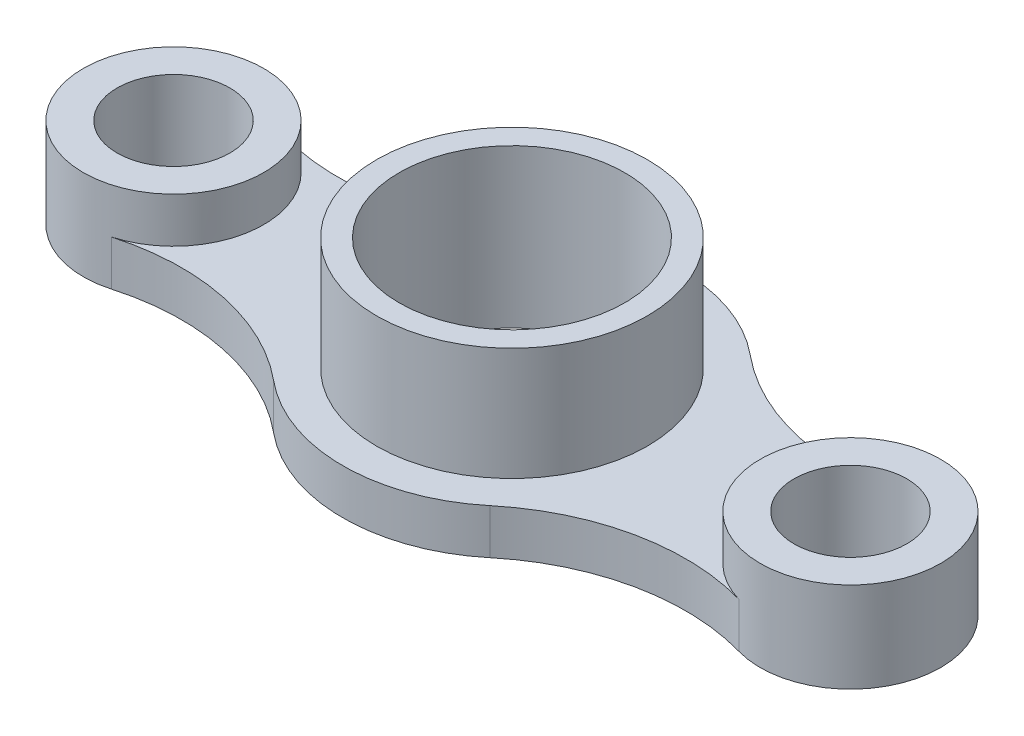
SolidWorks part; units mm, degrees
ref_plane "Front Plane" through (0, 0, 0) normal (0, 0, 1) x (1, 0, 0)
ref_plane "Top Plane" through (0, 0, 0) normal (0, 1, 0) x (1, 0, 0)
ref_plane "Right Plane" through (0, 0, 0) normal (1, 0, 0) x (0, 0, -1)
sketch "Sketch1" plane through (0, 0, 0) normal (0, 1, 0) x (1, 0, 0)
  line L0 (0, -5.5) -> (0, 5.5) construction
  circle A0 centre (0, 0) radius 50
  arc A1 (-139.0714, 38.4781) -> (-139.0714, -38.4781) centre (-150, 0) ccw
  circle A3 centre (0, 0) radius 60
  arc A4 (47.8929, 57.7172) -> (-47.8929, 57.7172) centre (0, 0) ccw
  circle A5 centre (-150, 0) radius 25
  arc A6 (-139.0714, 38.4781) -> (-47.8929, 57.7172) centre (-111.75, 134.6734) ccw
  arc A7 (-139.0714, -38.4781) -> (-47.8929, -57.7172) centre (-111.75, -134.6734) cw
  arc A8 (139.0714, -38.4781) -> (47.8929, -57.7172) centre (111.75, -134.6734) ccw
  arc A9 (139.0714, 38.4781) -> (47.8929, 57.7172) centre (111.75, 134.6734) cw
  circle A10 centre (150, 0) radius 25
  arc A11 (139.0714, 38.4781) -> (139.0714, -38.4781) centre (150, 0) cw
  arc A12 (-47.8929, -57.7172) -> (47.8929, -57.7172) centre (0, 0) ccw
  point P14 (-91.1042, 36.8279)
  dimension "D2" = 100
  dimension "D3" = 120
  dimension "D4" = 150
  dimension "D5" = 80
  dimension "D6" = 50
  dimension "D7" = 100
  dimension "D8" = 100
  dimension "D1" = 150
extrude "Boss-Extrude2" add sketch "Sketch1" along normal blind 20 contours A1 A7 A12 A8 A11 A9 A4 A6 | A3 | A10 | A5
extrude "Boss-Extrude3" add sketch "Sketch1<7>" along normal blind 70 contours A3 | A0
sketch "Sketch1<7>" plane through (0, 0, 0) normal (0, 1, 0) x (1, 0, 0) same geometry as "Sketch1"
sketch "Sketch3" plane through (0, 20, 0) normal (0, 1, 0) x (1, 0, 0)
  circle A0 centre (-150, 0) radius 40
  circle A1 centre (-150, 0) radius 25
  dimension "D1" = 80
  dimension "D2" = 50
extrude "Boss-Extrude4" add sketch "Sketch3" along normal blind 20
mirror "Mirror1" about plane through (0, 0, 0) normal (1, 0, 0) of "Boss-Extrude4"
